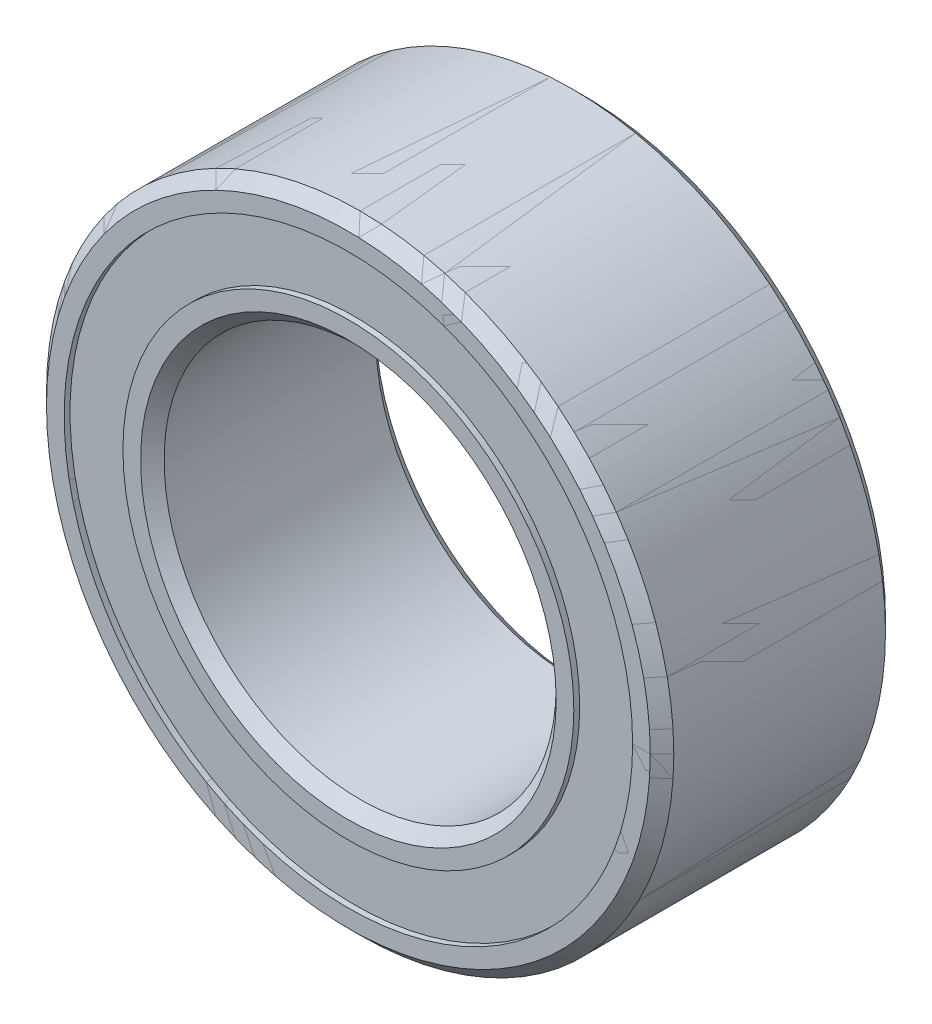
SolidWorks part; units mm, degrees
ref_plane "Front Plane" through (0, 0, 0) normal (0, 0, 1) x (1, 0, 0)
ref_plane "Top Plane" through (0, 0, 0) normal (0, 1, 0) x (1, 0, 0)
ref_plane "Right Plane" through (0, 0, 0) normal (1, 0, 0) x (0, 0, -1)
sketch "Sketch1" plane through (0, 0, 0) normal (1, 0, 0) x (0, 0, -1)
  line L0 (-1.5, 2.875) -> (1.5, 2.875) construction
  line L1 (-1.5, -2.875) -> (1.5, -2.875) construction
  line L2 (-1.5, 0) -> (1.5, 0) construction
  line L3 (0, 4) -> (0, -4) construction
  line L4 (0, 3.625) -> (0, 2.875) construction
  line L5 (1.5, 3.625) -> (-1.5, 3.625) construction
  line L7 (-1.5, -3.625) -> (1.5, -3.625) construction
  circle A0 centre (0, 3.25) radius 0.5 construction
  circle A2 centre (0, -3.25) radius 0.5 construction
  point P7 (0, 0)
  point P8 (0, -3.625)
  point P13 (0, -2.5)
  point P16 (0, -2.875)
  point P17 (-1.5, 0)
  point P18 (0, 2.5)
  point P19 (0, 3.625)
  point P29 (0, 2.875)
  dimension "Ball Dia" = 1
  dimension "ID" = 5
  dimension "Width" = 3
  dimension "OD" = 8
  dimension "Lo" = 7.25
  dimension "Li" = 5.75
sketch "Sketch8" plane through (0, 0, 0) normal (1, 0, 0) x (0, 0, -1)
  line L0 (-1.5, 0) -> (1.5, 0) construction
  line L2 (1.5, 4) -> (-1.5, 4)
  line L4 (-1.5, 4) -> (-1.5, 3.625)
  line L5 (-1.5, 3.625) -> (-0.3307, 3.625)
  line L6 (1.5, 3.625) -> (0.3307, 3.625)
  line L7 (1.5, 4) -> (1.5, 3.625)
  line L11 (1.5, 3.625) -> (-1.5, 3.625) construction
  circle A2 centre (0, 3.25) radius 0.5 construction
  arc A3 (0.3307, 3.625) -> (-0.3307, 3.625) centre (0, 3.25) ccw
revolve "Revolve1" add sketch "Sketch8" angle 360 about L0
chamfer "Chamfer1" distance 0.15 angle 45 2 edges at (4, 0, -1.5) (4, 0, 1.5)
sketch "Sketch2" plane through (0, 0, 0) normal (1, 0, 0) x (0, 0, -1)
  line L1 (1.35, 4) -> (1.35, -4) construction
  line L2 (0, 3.25) -> (1.5, 3.25) construction
  line L3 (-1.35, 4) -> (-1.35, -4) construction
  line L4 (-0.3307, 3.625) -> (-1.5, 3.625)
  line L6 (1.5, 2.875) -> (0.3307, 2.875)
  line L7 (-1.5, 2.65) -> (-1.5, 2.875)
  line L10 (1.5, 2.65) -> (1.5, 2.875)
  line L12 (1.35, 2.5) -> (-1.35, 2.5)
  line L13 (-1.35, 4) -> (-1.5, 3.85) construction
  line L14 (1.5, 3.85) -> (1.35, 4) construction
  line L15 (1.5, 4) -> (-1.5, 4) construction
  line L16 (1.5, 4) -> (1.5, 3.625) construction
  line L17 (-1.5, 4) -> (-1.5, 3.625) construction
  line L18 (1.5, 3.625) -> (-1.5, 3.625) construction
  line L19 (-1.35, 4) -> (-1.5, 3.85)
  line L20 (1.5, 3.85) -> (1.35, 4)
  line L21 (1.35, 4) -> (-1.35, 4)
  line L22 (1.5, 3.85) -> (1.5, 3.625)
  line L23 (-1.5, 3.85) -> (-1.5, 3.625)
  line L24 (1.5, 3.625) -> (0.3307, 3.625)
  line L25 (1.5, 2.65) -> (1.35, 2.5)
  line L26 (-1.35, 2.5) -> (-1.5, 2.65)
  line L27 (-0.3307, 2.875) -> (-1.5, 2.875)
  arc A0 (0.3307, 2.875) -> (-0.3307, 2.875) centre (0, 3.25) cw
  circle A4 centre (0, 3.25) radius 0.5 construction
  arc A5 (0.3307, 3.625) -> (-0.3307, 3.625) centre (0, 3.25) ccw
revolve "Revolve2" add sketch "Sketch2" angle 360 about L0
sketch "Sketch3" plane through (0, 0, 0) normal (1, 0, 0) x (0, 0, -1)
  line L0 (-0.5, 3.25) -> (0.5, 3.25)
  line L1 (0, 3.25) -> (0, 0) construction
  line L2 (0, 3.25) -> (1.5, 3.25) construction
  line L3 (-1.5, 0) -> (1.5, 0) construction
  circle A0 centre (0, 3.25) radius 0.5 construction
  arc A2 (0.5, 3.25) -> (-0.5, 3.25) centre (0, 3.25) ccw
  point P8 (0, 3.25)
  dimension "D1" = 1
  dimension "D2" = 3.25
revolve "Revolve3" add sketch "Sketch3" angle 360 about L0
ref_axis "Axis1" through (0, 0, -1.5) along (0, 0, 1)
pattern_circular "CirPattern1" count 11 every 32.727 about axis through (0, 0, -1.5) along (0, 0, 1) of bodies 104
sketch "Sketch5" plane through (0, 0, 0) normal (1, 0, 0) x (0, 0, -1)
  line L1 (1.5, 3.625) -> (-1.5, 3.625) construction
  line L2 (-1.5, 2.875) -> (1.5, 2.875) construction
  line L3 (-1.425, 3.625) -> (-0.5, 3.625)
  line L4 (-1.425, 3.625) -> (-1.425, 2.875)
  line L5 (-1.425, 2.875) -> (-0.5, 2.875)
  line L6 (-0.5, 3.625) -> (-0.5, 2.875)
  line L7 (0, 0) -> (0, 4) construction
  line L8 (0.5, 3.625) -> (0.5, 2.875)
  line L10 (-1.425, 3.925) -> (-1.425, 3.625) construction
  line L13 (1.425, 2.875) -> (0.5, 2.875)
  line L14 (1.425, 3.625) -> (1.425, 2.875)
  line L15 (1.425, 3.625) -> (0.5, 3.625)
  line L16 (-1.35, 4) -> (-1.5, 3.85) construction
  circle A1 centre (0, 3.25) radius 0.5 construction
revolve "Revolve5" add sketch "Sketch5" angle 360 about L0
sketch "Sketch6" plane through (0, 0, 0) normal (0, 1, 0) x (1, 0, 0)
  line L0 (4, -1.35) -> (4, 1.35) construction
  point P0 (4, -1.5)
  point P1 (4, 1.5)
  dimension "D1" = 3
sketch "Sketch9" plane through (0, 0, 0) normal (0, 0, 1) x (1, 0, 0)
  line L0 (0, -4) -> (0, 4) construction
  line L3 (0, -2.5) -> (0, 2.5) construction
  point P7 (0, 0)
  point P11 (0, 0)
  dimension "D1" = 8
  dimension "D2" = 5
equation "\"D2@CirPattern1\" = 360/\"Balls@CirPattern1\""
equation "\"D1@Sketch6\" = \"Width@Sketch1\""
equation "\"D1@Sketch9\"=\"OD@Sketch1\""
equation "\"D2@Sketch9\" = \"ID@Sketch1\""
equation "\"D1@Chamfer1\"=\"Width@Sketch1\" * .05"
